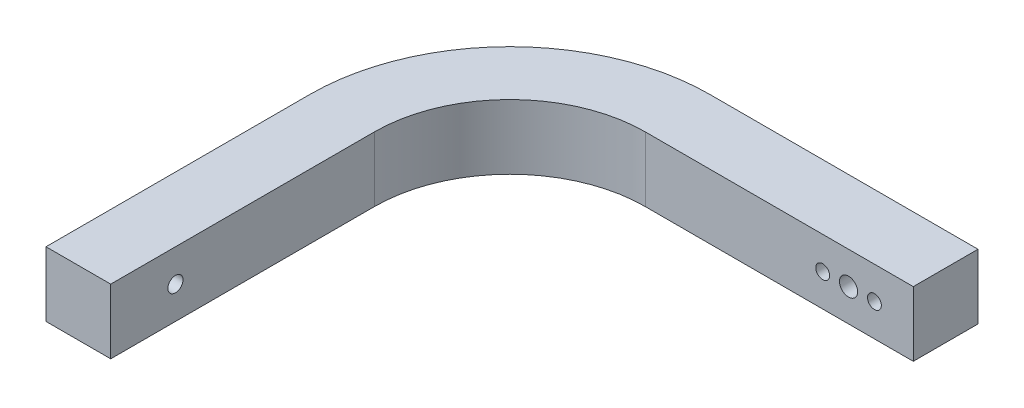
SolidWorks part; units mm, degrees
ref_plane "Front Plane" through (0, 0, 0) normal (0, 0, 1) x (1, 0, 0)
ref_plane "Top Plane" through (0, 0, 0) normal (0, 1, 0) x (1, 0, 0)
ref_plane "Right Plane" through (0, 0, 0) normal (1, 0, 0) x (0, 0, -1)
ref_axis "Z" through (0, 0, -5.375) along (0, 0, 1)
sketch "Sketch1" plane through (0, 0, 0) normal (0, 1, 0) x (1, 0, 0)
  line L0 (-47.1, 0) -> (47.1, 0) construction
  line L1 (-93.5, -46.4) -> (-93.5, -107.5)
  line L2 (-93.5, -107.5) -> (-78.5, -107.5)
  line L3 (-78.5, -107.5) -> (-78.5, -46.4)
  line L4 (-47.1, -15) -> (47.1, -15) construction
  line L5 (0, -15) -> (0, 0) construction
  line L6 (78.5, -107.5) -> (78.5, -46.4) construction
  line L7 (93.5, -107.5) -> (78.5, -107.5) construction
  line L8 (93.5, -46.4) -> (93.5, -107.5) construction
  line L9 (47.1, 0) -> (47.1, -15) construction
  line L10 (15, -15) -> (15, 0)
  line L11 (-47.1, -15) -> (15, -15)
  line L12 (-47.1, 0) -> (15, 0)
  line L13 (0, 5.375) -> (0, -112.875) construction
  arc A0 (-47.1, 0) -> (-93.5, -46.4) centre (-47.1, -46.4) ccw
  arc A1 (-78.5, -46.4) -> (-47.1, -15) centre (-47.1, -46.4) cw
  arc A2 (78.5, -46.4) -> (47.1, -15) centre (47.1, -46.4) ccw construction
  arc A3 (47.1, 0) -> (93.5, -46.4) centre (47.1, -46.4) cw construction
  point P10 (22.0594, -22.0981)
  dimension "D3" = 31.4
  dimension "D1" = 157
  dimension "D2" = 15
  dimension "D4" = 92.5
  dimension "D5" = 15
extrude "Boss-Extrude1" add sketch "Sketch1" along normal blind 7.5 and the other way blind 7.5
sketch "Sketch2" plane through (-78.5, 0, 0) normal (-1, 0, 0) x (0, 0, 1)
  line L1 (55, 0) -> (-55, 0) construction
  line L2 (0, -55) -> (0, 55) construction
  circle A0 centre (92.5, 0) radius 1.75
  dimension "D1" = 3.5
  dimension "D2" = 92.5
extrude "Cut-Extrude1" cut sketch "Sketch2" against normal through all both and the other way through all
ref_axis "Axis2" through (-120.1767, 0, 92.5) along (1, 0, 0)
sketch "Sketch3" plane through (0, 0, 0) normal (0, 0, -1) x (-1, 0, 0)
  line L0 (-6, 0) -> (6, 0) construction
  circle A0 centre (0, 0) radius 2.1
  circle A1 centre (-6, 0) radius 1.6
  circle A2 centre (6, 0) radius 1.6
  dimension "D1" = 4.2
  dimension "D3" = 3.2
  dimension "D2" = 12
extrude "Cut-Extrude2" cut sketch "Sketch3" against normal through all
sketch "Sketch4" plane through (-93.5, 0, 0) normal (1, 0, 0) x (0, 0, -1)
  circle A0 centre (-92.5, 0) radius 2.275
  circle A1 centre (-92.5, 0) radius 1.75 construction
  dimension "D1" = 4.55
extrude "Cut-Extrude3" cut sketch "Sketch4" along normal blind 6
sketch "Sketch5" plane through (-93.5, 0, 0) normal (-1, 0, 0) x (0, 0, 1)
  circle A0 centre (92.5, 0) radius 3.825
  dimension "D1" = 7.65
extrude "Cut-Extrude4" cut sketch "Sketch5" against normal blind 0.75
equation "\"width\"= \"EyeDiameter\" + \"EyeClearance\""
equation "\"prongwidth\"= \"L2Thickness\""
equation "\"D2@Sketch1\"=\"prongwidth\""
equation "\"D3@Sketch1\"=\"width\"/5"
equation "\"pronglength\"= \"BasePlaneDistance\"'model implicitly adds clearance (of prongwidth) to the hole drilled at the baseplanedistance"
equation "\"D4@Sketch1\"=\"pronglength\""
equation "\"D1@Boss-Extrude1\"=\"prongwidth\"/2"
equation "\"D2@Boss-Extrude1\"=\"prongwidth\"/2"
equation "\"lbracket-plane-to-axis\"= \"BasePlaneDistance\""
equation "\"D2@Sketch2\"=\"lbracket-plane-to-axis\""
equation "\"EyeDiameter\" = 155"
equation "\"BasePlaneDistance\" = \"EyeDiameter\"/2+15"
equation "\"EyeClearance\" = 2"
equation "\"D1@Sketch1\"=\"EyeDiameter\"+\"EyeClearance\""
equation "\"BearingDepth\"= 6"
equation "\"BearingHousingID\"=4.5"
equation "\"D1@Sketch4\"=\"BearingHousingID\" + \"PrinterFilamentThickness\" * \"ApplyPrinterOffset\" / 2"
equation "\"D1@Cut-Extrude3\"=\"BearingDepth\""
equation "\"BearingFlangeThickness\"= 0.75"
equation "\"BearingFlangeOD\"=7.5"
equation "\"D1@Sketch5\"=\"BearingFlangeOD\" + \"PrinterFilamentThickness\"*1.5 *\"ApplyPrinterOffset\""
equation "\"D1@Cut-Extrude4\"=\"BearingFlangeThickness\""
equation "\"PrinterFilamentThickness\"= 0.1"
equation "\"ApplyPrinterOffset\"= 1'if 1, adjust hole sizes to try and make pressfits work with the 3d printer"
equation "\"L2Thickness\" = 15"
equation "\"L2_ID\" = 20"
equation "\"vx\" = -3"
equation "\"vy\" = 3"
equation "\"vz\" = 10"
equation "\"parametric_end\" = 1"
equation "\"Rw_3_xx\" = -(\"vz\")/sqr((\"vx\")^2 + (\"vz\")^2)"
equation "\"Rw_3_xy\" = 0"
equation "\"Rw_3_xz\" = (\"vx\")/sqr((\"vx\")^2 + (\"vz\")^2)"
equation "\"Rw_3_zx\" = (\"vx\")/sqr((\"vx\")^2 + (\"vy\")^2 + (\"vz\")^2)"
equation "\"Rw_3_zy\" = (\"vy\")/sqr((\"vx\")^2 + (\"vy\")^2 + (\"vz\")^2)"
equation "\"Rw_3_zz\" = (\"vz\")/sqr((\"vx\")^2 + (\"vy\")^2 + (\"vz\")^2)"
equation "\"Rw_3_yx\" = (\"vx\")*(\"vy\")/sqr((\"vx\")^4 + (\"vx\")^2*(\"vy\")^2 + 2*(\"vx\")^2*(\"vz\")^2 + (\"vy\")^2*(\"vz\")^2 + (\"vz\")^4)"
equation "\"Rw_3_yy\" = -sqr((\"vx\")^2 + (\"vz\")^2)/sqr((\"vx\")^2 + (\"vy\")^2 + (\"vz\")^2)"
equation "\"Rw_3_yz\" = (\"vy\")*(\"vz\")/sqr((\"vx\")^4 + (\"vx\")^2*(\"vy\")^2 + 2*(\"vx\")^2*(\"vz\")^2 + (\"vy\")^2*(\"vz\")^2 + (\"vz\")^4)"
equation "\"O2Targx\" = -\"BasePlaneDistance\"*(\"vx\")*(\"vy\")/sqr((\"vx\")^4 + (\"vx\")^2*(\"vy\")^2 + 2*(\"vx\")^2*(\"vz\")^2 + (\"vy\")^2*(\"vz\")^2 + (\"vz\")^4)"
equation "\"O2Targy\" = \"BasePlaneDistance\"*sqr((\"vx\")^2 + (\"vz\")^2)/sqr((\"vx\")^2 + (\"vy\")^2 + (\"vz\")^2)"
equation "\"O2Targz\" = -\"BasePlaneDistance\"*(\"vy\")*(\"vz\")/sqr((\"vx\")^4 + (\"vx\")^2*(\"vy\")^2 + 2*(\"vx\")^2*(\"vz\")^2 + (\"vy\")^2*(\"vz\")^2 + (\"vz\")^4)"
equation "\"O2Targx_0\" = -(\"BasePlaneDistance\")*sqr((\"vx\")^2 + (\"vz\")^2)/sqr((\"vx\")^2 + (\"vy\")^2 + (\"vz\")^2)"
equation "\"O2Targy_0\" = -(\"BasePlaneDistance\")*(\"vy\")*(\"vz\")/sqr((\"vx\")^4 + (\"vx\")^2*(\"vy\")^2 + 2*(\"vx\")^2*(\"vz\")^2 + (\"vy\")^2*(\"vz\")^2 + (\"vz\")^4)"
equation "\"O2Targz_0\" = (\"BasePlaneDistance\")*(\"vx\")*(\"vy\")/sqr((\"vx\")^4 + (\"vx\")^2*(\"vy\")^2 + 2*(\"vx\")^2*(\"vz\")^2 + (\"vy\")^2*(\"vz\")^2 + (\"vz\")^4) + (\"BasePlaneDistance\")"
equation "\"theta2_s1\" = arcsin(((\"BasePlaneDistance\") - (\"O2Targz_0\"))/(\"BasePlaneDistance\")) + pi"
equation "\"theta2_s2\" = -arcsin(((\"BasePlaneDistance\") - (\"O2Targz_0\"))/(\"BasePlaneDistance\"))"
equation "\"theta1_s1\" = arcsin((\"O2Targy_0\")/((\"BasePlaneDistance\")*cos((\"Theta2\")))) + pi"
equation "\"theta1_s2\" = -arcsin((\"O2Targy_0\")/((\"BasePlaneDistance\")*cos((\"Theta2\"))))"
equation "\"theta1_s3\" = -arccos(-(\"O2Targx_0\")/((\"BasePlaneDistance\")*cos((\"Theta2\")))) + 2*pi"
equation "\"theta1_s4\" = arccos(-(\"O2Targx_0\")/((\"BasePlaneDistance\")*cos((\"Theta2\"))))"
equation "\"Theta1\" = \"theta1_s2\" 'so far, theta1_s1 and theta1_s4 have agreed, and they agree with the sw constraint solver"
equation "\"Theta2\" = \"theta2_s2\""
equation "\"o2_x\" = -(\"BasePlaneDistance\")*cos((\"Theta1\"))*cos((\"Theta2\"))"
equation "\"o2_y\" = -(\"BasePlaneDistance\")*sin((\"Theta1\"))*cos((\"Theta2\"))"
equation "\"o2_z\" = (\"BasePlaneDistance\")*(sin((\"Theta2\")) + 1)"
equation "\"o1_x\" = (\"BasePlaneDistance\")*sin((\"Theta1\"))"
equation "\"o1_y\" = -(\"BasePlaneDistance\")*cos((\"Theta1\"))"
equation "\"o1_z\" = (\"BasePlaneDistance\")"
equation "\"Actuator1_Theta\" = atn(\"vx\"/\"vz\") 'ik solution for the single link joint"
equation "\"Actuator2_Theta\" = \"Theta1\"  'ik solution for the double link joint"
